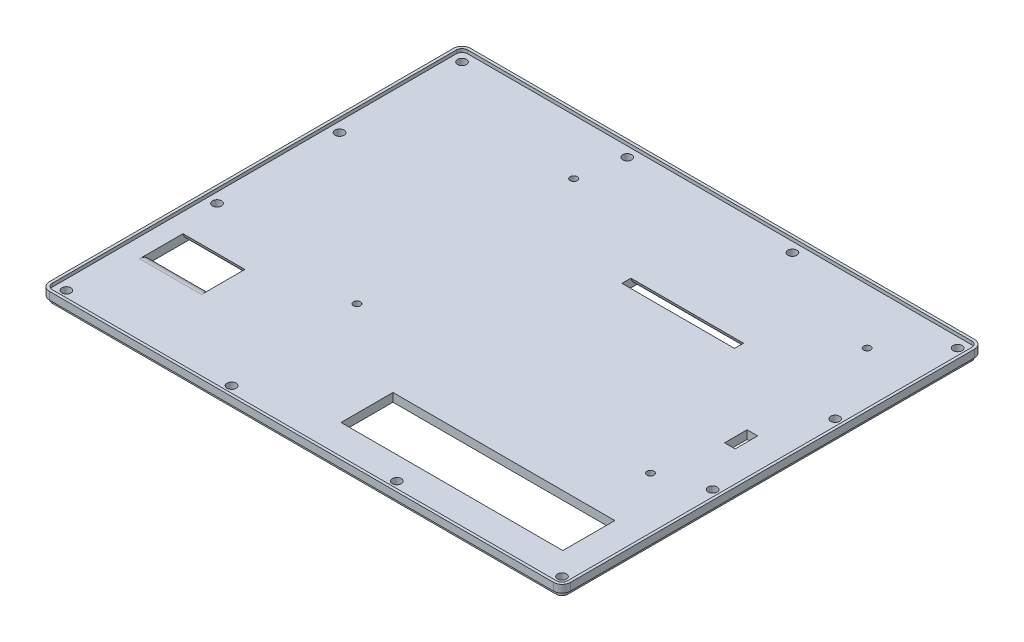
SolidWorks part; units mm, degrees
ref_plane "Front Plane" through (0, 0, 0) normal (0, 0, 1) x (1, 0, 0)
ref_plane "Top Plane" through (0, 0, 0) normal (0, 1, 0) x (1, 0, 0)
ref_plane "Right Plane" through (0, 0, 0) normal (1, 0, 0) x (0, 0, -1)
sketch "Sketch1" plane through (0, 0, 0) normal (0, 1, 0) x (1, 0, 0)
  line L1 (0, 0) -> (164.87, 0)
  line L2 (0, 0) -> (0, -104.3)
  line L3 (0, -104.3) -> (164.87, -104.3)
  line L4 (164.87, 0) -> (164.87, -104.3)
  line L5 (7.23, -7.46) -> (162.2, -7.46)
  line L6 (7.23, -7.46) -> (7.23, -101.93)
  line L7 (7.23, -101.93) -> (162.2, -101.93)
  line L8 (162.2, -7.46) -> (162.2, -101.93)
  line L9 (-4.77, 7.54) -> (174.2, 7.54)
  line L10 (-7.77, 4.54) -> (-7.77, -138.93)
  line L11 (-4.77, -141.93) -> (174.2, -141.93)
  line L12 (177.2, 4.54) -> (177.2, -138.93)
  arc A0 (174.2, -141.93) -> (177.2, -138.93) centre (174.2, -138.93) ccw
  arc A1 (-7.77, -138.93) -> (-4.77, -141.93) centre (-4.77, -138.93) ccw
  arc A2 (-4.77, 7.54) -> (-7.77, 4.54) centre (-4.77, 4.54) ccw
  arc A3 (174.2, 7.54) -> (177.2, 4.54) centre (174.2, 4.54) cw
  dimension "D11" = 3
  dimension "D1" = 104.3
  dimension "D2" = 164.87
  dimension "D3" = 2.67
  dimension "D4" = 2.37
  dimension "D5" = 7.46
  dimension "D6" = 7.23
  dimension "D7" = 15
  dimension "D8" = 15
  dimension "D9" = 15
  dimension "D10" = 40
extrude "Boss-Extrude1" add sketch "Sketch1" against normal blind 3 contours A3 L9 A2 L10 A1 L11 A0 L12 L1 L4 L3 L2 | L4 L1 L2 L3 L5 L8 L7 L6 | L8 L5 L6 L7 region at (82.435, 0, 1.9509) region at (84.715, 0, 54.695) region at (84.715, 0, -5.1619)
sketch "Sketch12" plane through (0, -3, 0) normal (0, -1, 0) x (1, 0, 0)
  line L0 (-4.77, -7.54) -> (174.2, -7.54)
  line L1 (177.2, -4.54) -> (177.2, 138.93)
  line L2 (-4.77, 141.93) -> (174.2, 141.93)
  line L3 (-7.77, -4.54) -> (-7.77, 138.93)
  line L8 (176.2, -4.54) -> (176.2, 138.93)
  line L9 (-4.77, -6.54) -> (174.2, -6.54)
  line L10 (176.2, -4.54) -> (176.2, 138.93)
  line L11 (-4.77, -6.54) -> (174.2, -6.54)
  line L18 (-6.77, -4.54) -> (-6.77, 138.93)
  line L19 (-4.77, 140.93) -> (174.2, 140.93)
  line L20 (-6.77, -4.54) -> (-6.77, 138.93)
  line L21 (-4.77, 140.93) -> (174.2, 140.93)
  arc A0 (174.2, -7.54) -> (177.2, -4.54) centre (174.2, -4.54) ccw
  arc A1 (177.2, 138.93) -> (174.2, 141.93) centre (174.2, 138.93) ccw
  arc A2 (-4.77, 141.93) -> (-7.77, 138.93) centre (-4.77, 138.93) ccw
  arc A3 (-7.77, -4.54) -> (-4.77, -7.54) centre (-4.77, -4.54) ccw
  arc A6 (176.2, 138.93) -> (174.2, 140.93) centre (174.2, 138.93) ccw
  arc A7 (174.2, -6.54) -> (176.2, -4.54) centre (174.2, -4.54) ccw
  arc A8 (176.2, 138.93) -> (174.2, 140.93) centre (174.2, 138.93) ccw
  arc A9 (174.2, -6.54) -> (176.2, -4.54) centre (174.2, -4.54) ccw
  arc A14 (-6.77, -4.54) -> (-4.77, -6.54) centre (-4.77, -4.54) ccw
  arc A15 (-4.77, 140.93) -> (-6.77, 138.93) centre (-4.77, 138.93) ccw
  arc A16 (-6.77, -4.54) -> (-4.77, -6.54) centre (-4.77, -4.54) ccw
  arc A17 (-4.77, 140.93) -> (-6.77, 138.93) centre (-4.77, 138.93) ccw
  dimension "D1" = 1
  dimension "D2" = 1
  dimension "D3" = 1
extrude "Cut-Extrude9" cut sketch "Sketch12" against normal blind 1.5
sketch "Sketch8" plane through (0, -3, 0) normal (0, -1, 0) x (1, 0, 0)
  line L1 (86.11, 110.85) -> (164.87, 110.85)
  line L2 (86.11, 110.85) -> (86.11, 129.3)
  line L3 (86.11, 129.3) -> (164.87, 129.3)
  line L4 (164.87, 110.85) -> (164.87, 129.3)
  line L6 (174.2, 141.93) -> (-4.77, 141.93) construction
  line L9 (177.2, -4.54) -> (177.2, 138.93) construction
  dimension "D1" = 91.09
  dimension "D2" = 12.63
  dimension "D3" = 18.45
  dimension "D4" = 12.33
extrude "Cut-Extrude7" cut sketch "Sketch8" against normal through all
sketch "Sketch3" plane through (0, -3, 0) normal (0, -1, 0) x (-1, 0, 0)
  line L5 (0, -110.85) -> (-22, -110.85)
  line L6 (0, -110.85) -> (0, -104.3)
  line L7 (0, -104.3) -> (-22, -104.3)
  line L8 (-22, -110.85) -> (-22, -104.3)
  line L11 (-174.2, -141.93) -> (4.77, -141.93) construction
  line L13 (7.77, -138.93) -> (7.77, 4.54) construction
  dimension "D1" = 6.55
  dimension "D2" = 22
  dimension "D3" = 31.08
  dimension "D4" = 7.77
extrude "Cut-Extrude4" cut sketch "Sketch3" against normal through all contours L8 L6 region at (11, -3, 107.575)
sketch "Sketch2" plane through (0, -3, 0) normal (0, -1, 0) x (1, 0, 0)
  line L0 (-7.77, -4.54) -> (-7.77, 138.93) construction
  line L1 (-4.77, -7.54) -> (174.2, -7.54) construction
  line L2 (177.2, -4.54) -> (177.2, 138.93) construction
  line L3 (-4.77, 141.93) -> (174.2, 141.93) construction
  circle A0 centre (-3.27, -3.04) radius 1.6
  circle A1 centre (172.7, -3.04) radius 1.6
  circle A2 centre (172.7, 137.43) radius 1.6
  circle A3 centre (-3.27, 137.43) radius 1.6
  circle A4 centre (-3.27, 40.45) radius 1.6
  circle A5 centre (-3.27, 83.94) radius 1.6
  circle A6 centre (172.7, 40.45) radius 1.6
  circle A7 centre (172.7, 83.94) radius 1.6
  circle A8 centre (114.05, -3.04) radius 1.6
  circle A9 centre (55.38, -3.04) radius 1.6
  circle A10 centre (114.05, 137.43) radius 1.6
  circle A11 centre (55.38, 137.43) radius 1.6
  dimension "D1" = 3.2
  dimension "D4" = 3.2
  dimension "D6" = 3.2
  dimension "D8" = 3.2
  dimension "D9" = 3.2
  dimension "D10" = 3.2
  dimension "D13" = 3.2
  dimension "D14" = 3.2
  dimension "D17" = 3.2
  dimension "D18" = 3.2
  dimension "D19" = 3.2
  dimension "D20" = 3.2
  dimension "D2" = 4.5
  dimension "D3" = 4.5
  dimension "D5" = 4.5
  dimension "D7" = 4.5
  dimension "D11" = 43.49
  dimension "D12" = 43.49
  dimension "D21" = 58.65
  dimension "D22" = 58.65
extrude "Cut-Extrude3" cut sketch "Sketch2" against normal up to next contours A1 | A8 | A0 | A5 | A3 | A11 | A10 | A2 | A7 | A6 | A9 | A4 region at (-3.27, -3, -3.04) region at (172.7, -3, -3.04) region at (172.7, -3, 137.43) region at (-3.27, -3, 137.43) region at (-3.27, -3, 83.94) region at (172.7, -3, 40.45) region at (172.7, -3, 83.94) region at (114.05, -3, -3.04) region at (114.05, -3, 137.43) region at (55.38, -3, 137.43)
extrude "Boss-Extrude2" add sketch "Sketch12<2>" against normal blind 1.2 from surface starting at face at (172.7, 0, 85.54)
sketch "Sketch12<2>" plane through (0, -3, 0) normal (0, -1, 0) x (1, 0, 0) same geometry as "Sketch12"
sketch "Sketch13" plane through (0, -3, 0) normal (0, -1, 0) x (-1, 0, 0)
  line L0 (-177.2, 4.54) -> (-177.2, -138.93) construction
  line L1 (-164.2, -59.46) -> (-160.45, -59.46)
  line L2 (-164.2, -59.46) -> (-164.2, -67.46)
  line L3 (-164.2, -67.46) -> (-160.45, -67.46)
  line L4 (-160.45, -59.46) -> (-160.45, -67.46)
  line L5 (4.77, 7.54) -> (-174.2, 7.54) construction
  line L7 (-133.2, -33.46) -> (-93.2, -33.46)
  line L8 (-133.2, -33.46) -> (-133.2, -36.66)
  line L9 (-133.2, -36.66) -> (-93.2, -36.66)
  line L10 (-93.2, -33.46) -> (-93.2, -36.66)
  line L11 (-22, -104.3) -> (0, -104.3)
  line L12 (-22, -104.3) -> (-22, -99.3)
  line L13 (-22, -99.3) -> (0, -99.3)
  line L14 (0, -104.3) -> (0, -99.3)
  dimension "D1" = 3.75
  dimension "D2" = 8
  dimension "D3" = 13
  dimension "D4" = 67
  dimension "D5" = 40
  dimension "D6" = 3.2
  dimension "D7" = 44
  dimension "D8" = 41
  dimension "D9" = 5
  dimension "D10" = 22
extrude "Cut-Extrude10" cut sketch "Sketch13" against normal through all
fillet "Fillet1" radius 4 3 edges at (113.2, -3, 33.46) (11, 0, 110.85) (11, -3, 99.3)
sketch "Sketch15" plane through (0, -3, 0) normal (0, -1, 0) x (1, 0, 0)
  line L0 (177.2, -4.54) -> (177.2, 138.93) construction
  line L1 (-4.77, -7.54) -> (174.2, -7.54) construction
  circle A0 centre (156.64, 13.02) radius 4.15
  circle A1 centre (52.44, 13.02) radius 4.15
  circle A2 centre (156.64, 89.96) radius 4.15
  circle A3 centre (52.44, 89.96) radius 4.15
  point P8 (0, 0)
  point P9 (0, 0)
  point P10 (0, 0)
  point P11 (0, 0)
  point P12 (0, 0)
  point P13 (0, 0)
  dimension "D1" = 8.3
  dimension "D2" = 8.3
  dimension "D3" = 8.3
  dimension "D4" = 8.3
  dimension "D5" = 76.94
  dimension "D6" = 104.2
  dimension "D7" = 20.56
  dimension "D8" = 20.56
extrude "Boss-Extrude3" add sketch "Sketch15" along normal blind 2.2
sketch "Sketch16" plane through (0, -5.2, 0) normal (0, -1, 0) x (1, 0, 0)
  circle A0 centre (156.64, 13.02) radius 1.25
  circle A1 centre (156.64, 89.96) radius 1.25
  circle A2 centre (52.44, 89.96) radius 1.25
  circle A3 centre (52.44, 13.02) radius 1.25
  dimension "D1" = 2.5
  dimension "D2" = 2.5
  dimension "D3" = 2.5
  dimension "D4" = 2.5
extrude "Cut-Extrude11" cut sketch "Sketch16" against normal through all
